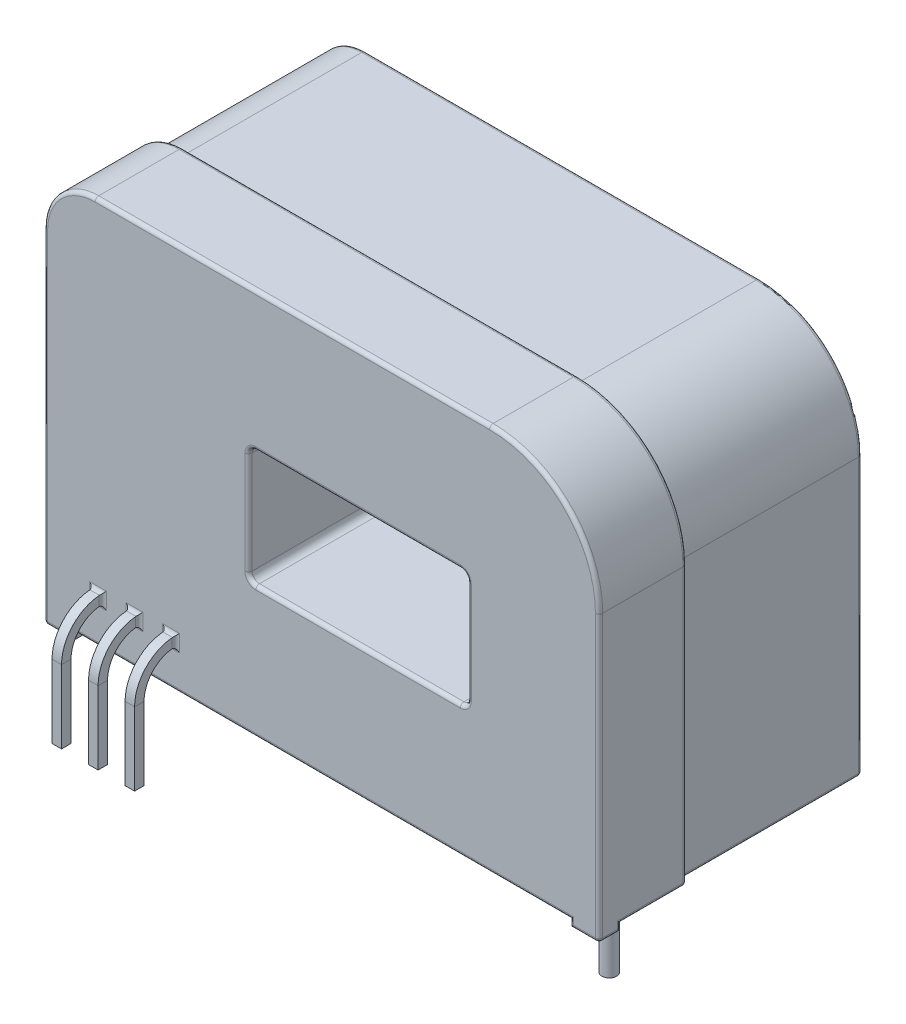
SolidWorks part; units mm, degrees
ref_plane "Front Plane" through (0, 0, 0) normal (0, 0, 1) x (1, 0, 0)
ref_plane "Top Plane" through (0, 0, 0) normal (0, 1, 0) x (1, 0, 0)
ref_plane "Right Plane" through (0, 0, 0) normal (1, 0, 0) x (0, 0, -1)
sketch "Sketch1" plane through (0, 0, 0) normal (0, 0, 1) x (1, 0, 0)
  line L0 (0, 0) -> (0, 23.5)
  line L1 (3.5, 27) -> (30.5, 27)
  line L2 (38, 19.5) -> (38, 0)
  line L3 (38, 0) -> (36, 0)
  line L4 (36, 0) -> (36, 0.5)
  line L5 (36, 0.5) -> (2, 0.5)
  line L6 (2, 0.5) -> (2, 0)
  line L7 (2, 0) -> (0, 0)
  line L8 (2, 0.5) -> (0, 0.5)
  line L9 (14.5, 17.5) -> (28.5, 17.5)
  line L10 (14, 17) -> (14, 10)
  line L11 (14.5, 9.5) -> (28.5, 9.5)
  line L12 (29, 17) -> (29, 10)
  line L13 (36, 0.5) -> (38, 0.5)
  line L14 (20, 0.5) -> (20, 0)
  line L15 (20, 0) -> (18, 0)
  line L16 (18, 0) -> (18, 0.5)
  arc A0 (0, 23.5) -> (3.5, 27) centre (3.5, 23.5) cw
  arc A1 (30.5, 27) -> (38, 19.5) centre (30.5, 19.5) cw
  arc A2 (14.5, 17.5) -> (14, 17) centre (14.5, 17) ccw
  arc A3 (14, 10) -> (14.5, 9.5) centre (14.5, 10) ccw
  arc A4 (28.5, 9.5) -> (29, 10) centre (28.5, 10) ccw
  arc A5 (28.5, 17.5) -> (29, 17) centre (28.5, 17) cw
  point P19 (14, 17.5)
  point P22 (14, 9.5)
  point P27 (29, 17.5)
  point P34 (19, 0.5)
  point P35 (19, 0)
  point P36 (18, 0)
  point P37 (17.4971, 0.5)
  dimension "D1" = 27
  dimension "D5" = 3.5
  dimension "D6" = 7.5
  dimension "D11" = 0.5
  dimension "D2" = 38
  dimension "D3" = 2
  dimension "D4" = 0.5
  dimension "D7" = 8
  dimension "D8" = 15
  dimension "D9" = 9
  dimension "D10" = 9.5
extrude "Boss-Extrude1" add sketch "Sketch1" against normal blind 6 contours A1 L1 A0 L0 L8 L5 L13 L2 L9 A5 L12 A4 L11 A3 L10 A2 region at (0.4633, 12, 0)
extrude "Boss-Extrude2" add sketch "Sketch1<3>" against normal blind 1.5 contours L6 L8 L0 L7 | L13 L4 L3 L2 region at (1, 0.25, 0) region at (37, 0.25, 0)
sketch "Sketch1<3>" plane through (0, 0, 0) normal (0, 0, 1) x (1, 0, 0) same geometry as "Sketch1"
sketch "Sketch2" plane through (0, 0, -6) normal (0, 0, -1) x (-1, 0, 0)
  line L3 (-37.5, 0.5) -> (-0.5, 0.5)
  line L6 (-0.5, 0.5) -> (-0.5, 23.5)
  line L7 (-3.5, 26.5) -> (-30.5, 26.5)
  line L8 (-37.5, 19.5) -> (-37.5, 0.5)
  line L9 (-0.5, 0.5) -> (-0.5, 23.5)
  line L10 (-3.5, 26.5) -> (-30.5, 26.5)
  line L11 (-37.5, 19.5) -> (-37.5, 0.5)
  line L14 (-14.5, 17.5) -> (-28.5, 17.5)
  line L15 (-14, 10) -> (-14, 17)
  line L16 (-28.5, 9.5) -> (-14.5, 9.5)
  line L17 (-29, 17) -> (-29, 10)
  line L18 (-14.5, 17.5) -> (-28.5, 17.5)
  line L19 (-14, 10) -> (-14, 17)
  line L20 (-28.5, 9.5) -> (-14.5, 9.5)
  line L21 (-29, 17) -> (-29, 10)
  arc A4 (-0.5, 23.5) -> (-3.5, 26.5) centre (-3.5, 23.5) ccw
  arc A5 (-30.5, 26.5) -> (-37.5, 19.5) centre (-30.5, 19.5) ccw
  arc A6 (-0.5, 23.5) -> (-3.5, 26.5) centre (-3.5, 23.5) ccw
  arc A7 (-30.5, 26.5) -> (-37.5, 19.5) centre (-30.5, 19.5) ccw
  arc A10 (-14, 17) -> (-14.5, 17.5) centre (-14.5, 17) ccw
  arc A11 (-14.5, 9.5) -> (-14, 10) centre (-14.5, 10) ccw
  arc A12 (-29, 10) -> (-28.5, 9.5) centre (-28.5, 10) ccw
  arc A13 (-28.5, 17.5) -> (-29, 17) centre (-28.5, 17) ccw
  arc A14 (-14, 17) -> (-14.5, 17.5) centre (-14.5, 17) ccw
  arc A15 (-14.5, 9.5) -> (-14, 10) centre (-14.5, 10) ccw
  arc A16 (-29, 10) -> (-28.5, 9.5) centre (-28.5, 10) ccw
  arc A17 (-28.5, 17.5) -> (-29, 17) centre (-28.5, 17) ccw
  dimension "D2" = 0
  dimension "D1" = 0.5
extrude "Boss-Extrude3" add sketch "Sketch2" along normal offset from surface (12.5 mm away) 18.5 up to face at (18.6828, 10.0278, 0)
extrude "Boss-Extrude4" add sketch "Sketch1<4>" along normal blind 1.5 from surface contours L16 L15 L14 L5 region at (19, 0.25, 0) starting at face at (21.5, 13.5, -18.5)
sketch "Sketch1<4>" plane through (0, 0, 0) normal (0, 0, 1) x (1, 0, 0) same geometry as "Sketch1"
sketch "Sketch3" plane through (0, 0, 0) normal (0, -1, 0) x (1, 0, 0)
  line L0 (5.875, 2.825) -> (5.875, 2.175)
  line L1 (3.375, 2.825) -> (4.025, 2.825)
  line L2 (3.375, 2.825) -> (3.375, 2.175)
  line L3 (3.375, 2.175) -> (4.025, 2.175)
  line L4 (4.025, 2.825) -> (4.025, 2.175)
  line L5 (5.875, 2.825) -> (6.525, 2.825)
  line L6 (6.525, 2.825) -> (6.525, 2.175)
  line L7 (5.875, 2.175) -> (6.525, 2.175)
  line L8 (8.375, 2.825) -> (8.375, 2.175)
  line L9 (8.375, 2.825) -> (9.025, 2.825)
  line L10 (9.025, 2.825) -> (9.025, 2.175)
  line L11 (8.375, 2.175) -> (9.025, 2.175)
  line L12 (3.375, 2.825) -> (4.025, 2.175) construction
  line L13 (36, 0) -> (2, 0) construction
  line L15 (8.375, 2.825) -> (9.025, 2.175) construction
  line L16 (21.5, 0) -> (21.5, -18.5) construction
  line L17 (20, -18.5) -> (18, -18.5) construction
  line L18 (14.5, 0) -> (28.5, 0) construction
  line L19 (14.5, 0) -> (28.5, 0) construction
  circle A0 centre (7, -14.7) radius 0.5
  circle A1 centre (36, -2.7) radius 0.5
  point P4 (3.7, 2.5)
  point P17 (8.7, 2.5)
  dimension "D5" = 1
  dimension "D7" = 1
  dimension "D9" = 14.5
  dimension "D1" = 0.65
  dimension "D2" = 3
  dimension "D3" = 2.5
  dimension "D4" = 2.5
  dimension "D6" = 12.8
  dimension "D8" = 14.5
  dimension "D10" = 5.2
  dimension "D11" = 12
extrude "Boss-Extrude5" add sketch "Sketch3" along normal blind 4 and the other way up to surface (0.5 mm away) other way up to face at (19, 0.5, -8.625)
sketch "Sketch4" plane through (3.375, 0, 0) normal (-1, 0, 0) x (0, 0, 1)
  line L0 (2.175, 0) -> (2.175, 1)
  line L1 (2.825, 0) -> (2.175, 0) construction
  line L2 (2.175, 0.5) -> (2.175, -4) construction
  line L3 (0, 0) -> (0, 23.5) construction
  line L4 (0, 3.175) -> (-8.3093, 3.175) construction
  arc A0 (2.175, 1) -> (0, 3.175) centre (0, 1) ccw
  point P11 (0, 3.5764)
  dimension "D1" = 1
sketch "Sketch5" plane through (0, 0, 0) normal (0, -1, 0) x (1, 0, 0)
  line L0 (9.025, 2.825) -> (8.375, 2.825) construction
  line L1 (8.375, 2.825) -> (8.375, 2.175) construction
  line L2 (8.375, 2.175) -> (9.025, 2.175) construction
  line L3 (9.025, 2.175) -> (9.025, 2.825) construction
  line L4 (6.525, 2.825) -> (5.875, 2.825) construction
  line L5 (5.875, 2.825) -> (5.875, 2.175) construction
  line L6 (5.875, 2.175) -> (6.525, 2.175) construction
  line L7 (6.525, 2.175) -> (6.525, 2.825) construction
  line L8 (3.375, 2.825) -> (3.375, 2.175) construction
  line L9 (3.375, 2.175) -> (4.025, 2.175) construction
  line L10 (4.025, 2.175) -> (4.025, 2.825) construction
  line L11 (4.025, 2.825) -> (3.375, 2.825) construction
  line L12 (9.025, 2.825) -> (8.375, 2.825)
  line L13 (8.375, 2.825) -> (8.375, 2.175)
  line L14 (8.375, 2.175) -> (9.025, 2.175)
  line L15 (9.025, 2.175) -> (9.025, 2.825)
  line L16 (6.525, 2.825) -> (5.875, 2.825)
  line L17 (5.875, 2.825) -> (5.875, 2.175)
  line L18 (5.875, 2.175) -> (6.525, 2.175)
  line L19 (6.525, 2.175) -> (6.525, 2.825)
  line L20 (3.375, 2.825) -> (3.375, 2.175)
  line L21 (3.375, 2.175) -> (4.025, 2.175)
  line L22 (4.025, 2.175) -> (4.025, 2.825)
  line L23 (4.025, 2.825) -> (3.375, 2.825)
sweep "Sweep2" add profiles "Sketch5" path "Sketch4"
fillet "Fillet1" radius 0.25 66 edges at (1.0251, 25.9749, -6) (17, 27, -6) (35.8033, 24.8033, -6) (1.3787, 25.6213, -6) (17, 26.5, -6) (37.5, 10, -6) (37.5, 0.5, -12.25) (0.5, 12, -6) (0.5, 0.5, -12.25) (0, 0, -0.75) (0, 0.25, -1.5) (0, 0.5, -3.75) (0, 12, -6) (38, 10, -6) (38, 0.5, -3.75) (38, 0.25, -1.5) (38, 0, -0.75) (3.7, 3.175, 0) (4.025, 3.5, 0) (3.7, 3.825, 0) (3.375, 3.5, 0) (5.875, 3.5, 0) (6.2, 3.175, 0) (6.525, 3.5, 0) (6.2, 3.825, 0) (14.1464, 17.3536, 0) (14, 13.5, 0) (14.1464, 9.6464, 0) (21.5, 9.5, 0) (28.8536, 9.6464, 0) (29, 13.5, 0) (28.8536, 17.3536, 0) (21.5, 17.5, 0) (38, 9.75, 0) (37, 0, 0) (36, 0.25, 0) (19, 0.5, 0) (2, 0.25, 0) (1, 0, 0) (0, 11.75, 0) (1.0251, 25.9749, 0) (17, 27, 0) (35.8033, 24.8033, 0) (8.7, 3.825, 0) (8.375, 3.5, 0) (8.7, 3.175, 0) (9.025, 3.5, 0) (0.5, 12, -18.5) (9.25, 0.5, -18.5) (18, 0.25, -18.5) (19, 0, -18.5) (20, 0.25, -18.5) (28.75, 0.5, -18.5) (37.5, 10, -18.5) (35.4497, 24.4497, -18.5) (17, 26.5, -18.5) (1.3787, 25.6213, -18.5) (29, 13.5, -18.5) (28.8536, 9.6464, -18.5) (21.5, 9.5, -18.5) (14.1464, 9.6464, -18.5) (14, 13.5, -18.5) (14.1464, 17.3536, -18.5) (21.5, 17.5, -18.5) (28.8536, 17.3536, -18.5) (35.4497, 24.4497, -6)
